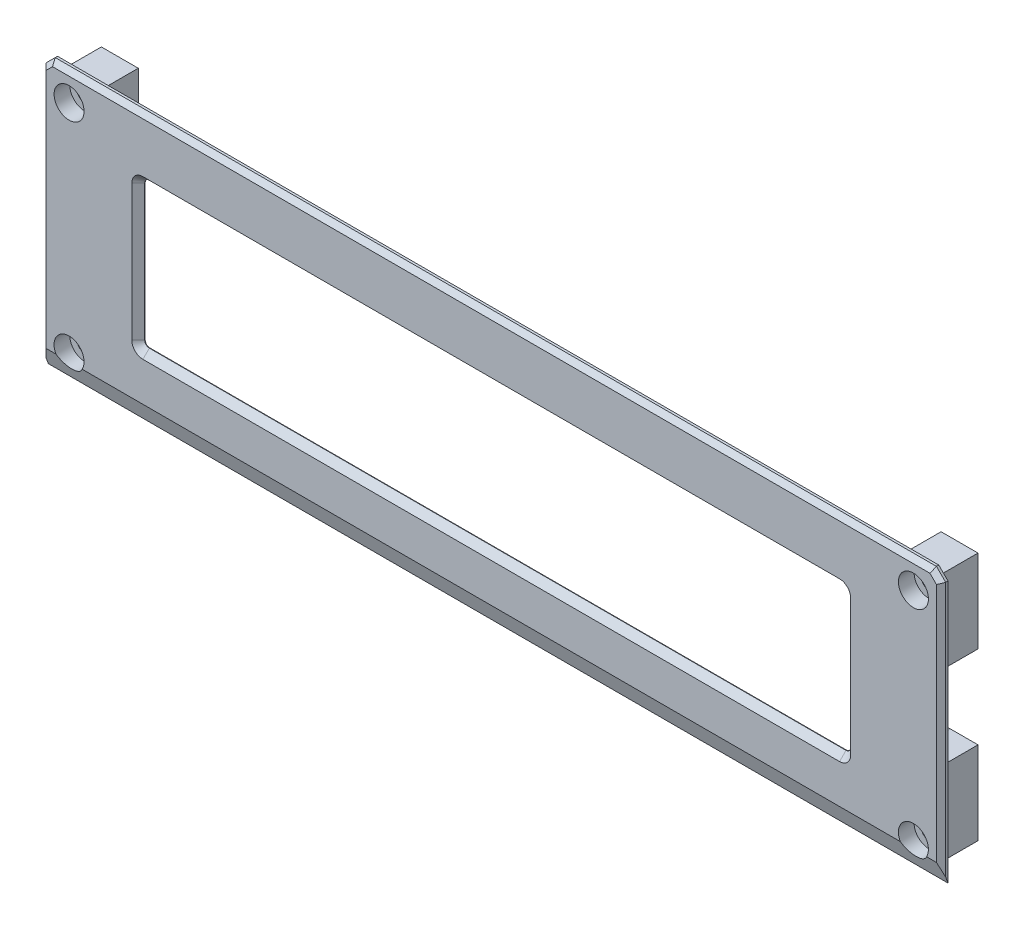
SolidWorks part; units mm, degrees
material "6061-T6 (SS)"
ref_plane "Front Plane" through (0, 0, 0) normal (0, 0, 1) x (1, 0, 0)
ref_plane "Top Plane" through (0, 0, 0) normal (0, 1, 0) x (1, 0, 0)
ref_plane "Right Plane" through (0, 0, 0) normal (1, 0, 0) x (0, 0, -1)
sketch "Croquis1" plane through (0, 0, 0) normal (0, 0, 1) x (1, 0, 0)
  line L0 (-78, 17.26) -> (78, 17.26) construction
  line L1 (-97.5, 29.5) -> (97.5, 29.5)
  line L2 (-97.5, 29.5) -> (-97.5, -29.2)
  line L3 (-97.5, -29.2) -> (97.5, -29.2)
  line L4 (97.5, 29.5) -> (97.5, -29.2)
  line L5 (-76.5, 16.26) -> (76.5, 16.26)
  line L6 (-76.5, 16.26) -> (-76.5, -15.24)
  line L7 (-76.5, -15.24) -> (76.5, -15.24)
  line L8 (76.5, 16.26) -> (76.5, -15.24)
  line L9 (78, -15.74) -> (-78, -15.74) construction
  line L10 (-81.5, -12.24) -> (-81.5, 13.76) construction
  line L11 (81.5, 13.76) -> (81.5, -12.24) construction
  line L14 (-97.5, 27.5) -> (-97.5, -29.2) construction
  line L15 (95.5, 29.5) -> (-95.5, 29.5) construction
  dimension "D1" = 1
  dimension "D2" = 0.5
  dimension "D3" = 5
  dimension "D4" = 5
extrude "Saliente-Extruir1" add sketch "Croquis1" along normal blind 1.5
fillet "Redondeo1" radius 1 4 edges at (-76.5, -15.24, 0.75) (76.5, -15.24, 0.75) (76.5, 16.26, 0.75) (-76.5, 16.26, 0.75)
chamfer "Chaflán1" distance 1.4 angle 45 8 edges at (0, -15.24, 1.5) (76.5, 0.51, 1.5) (0, 16.26, 1.5) (-76.5, 0.51, 1.5) (76.2071, 15.9671, 1.5) (76.2071, -14.9471, 1.5) (-76.2071, 15.9671, 1.5) (-76.2071, -14.9471, 1.5)
sketch "Croquis2" plane through (97.5, 0, 0) normal (1, 0, 0) x (0, 0, -1)
  line L0 (0, -29.2) -> (-1.5, -25.0788)
  line L1 (2.3196, -35.573) -> (0, -29.2) construction
  line L2 (0, -29.2) -> (-1.5, -29.2)
  line L3 (-1.5, -29.2) -> (-1.5, -25.0788)
  line L4 (-1.5, -29.2) -> (-1.5, 29.5) construction
extrude "Cortar-Extruir1" cut sketch "Croquis2" against normal through all
sketch "Croquis3" plane through (0, 0, 0) normal (0, 0, -1) x (-1, 0, 0)
  line L1 (-95, 27) -> (-87, 27)
  line L2 (-95, 27) -> (-95, 9)
  line L3 (-95, 9) -> (-87, 9)
  line L4 (-87, 27) -> (-87, 9)
  line L5 (-95, -27) -> (-87, -27)
  line L6 (-95, -27) -> (-95, -9)
  line L7 (-95, -9) -> (-87, -9)
  line L8 (-87, -27) -> (-87, -9)
  line L9 (95, 27) -> (87, 27)
  line L10 (95, 27) -> (95, 17)
  line L11 (95, 17) -> (87, 17)
  line L12 (87, 27) -> (87, 17)
  line L13 (95, -27) -> (87, -27)
  line L14 (95, -27) -> (95, -17)
  line L15 (95, -17) -> (87, -17)
  line L16 (87, -27) -> (87, -17)
  dimension "D1" = 8
  dimension "D2" = 18
  dimension "D3" = 18
  dimension "D4" = 10
  dimension "D5" = 10
extrude "Saliente-Extruir2" add sketch "Croquis3" along normal blind 9
sketch "Croquis4" plane through (0, 0, 0) normal (0, 0, -1) x (-1, 0, 0)
  line L0 (-87, 9) -> (-87, 27) construction
  line L1 (87, 27) -> (-87, 27)
  line L2 (87, 27) -> (87, 23)
  line L3 (87, 23) -> (-87, 23)
  line L4 (-87, 27) -> (-87, 23)
  line L5 (87, -17) -> (87, -27) construction
  line L6 (-87, -27) -> (87, -27)
  line L7 (-87, -27) -> (-87, -23)
  line L8 (-87, -23) -> (87, -23)
  line L9 (87, -27) -> (87, -23)
  line L10 (-95, 9) -> (-87, 9) construction
  line L11 (-95, -9) -> (-91, -9)
  line L12 (-95, -9) -> (-95, 9)
  line L13 (-95, 9) -> (-91, 9)
  line L14 (-91, -9) -> (-91, 9)
  line L15 (87, 17) -> (95, 17) construction
  line L16 (95, -17) -> (91, -17)
  line L17 (95, -17) -> (95, 17)
  line L18 (95, 17) -> (91, 17)
  line L19 (91, -17) -> (91, 17)
  point P12 (87, -25)
  dimension "D1" = 4
  dimension "D2" = 4
  dimension "D3" = 4
  dimension "D4" = 4
extrude "Saliente-Extruir3" add sketch "Croquis4" along normal blind 2
fillet "Redondeo2" radius 2 12 edges at (-87, 17, -4.5) (-87, -17, -4.5) (87, -9, -4.5) (87, 9, -4.5) (91, -9, -1) (87, -23, -1) (-87, -23, -1) (-91, -17, -1) (-91, 17, -1) (-87, 23, -1) (87, 23, -1) (91, 9, -1)
hole_wizard "Refrentado para tornillo con cabeza hueca de M31" positions "Croquis5" profile "Croquis7" counterbore size "M3" standard "DIN" end condition through all
sketch "Croquis5" plane through (0, 0, 1.5) normal (0, 0, 1) x (1, 0, 0)
  point P0 (-91.5, 23.5)
  point P3 (-91.5, -23.5)
  point P6 (91.5, -23.5)
  point P9 (91.5, 23.5)
sketch "Croquis7" plane through (-91.5, 23.5, 1.5) normal (1, 0, 0) x (0, -1, 0)
  line L0 (0, 0) -> (0, 10.5)
  line L1 (0, 10.5) -> (1.7, 10.5)
  line L3 (1.7, 10.5) -> (1.7, 3.4)
  line L4 (1.7, 3.4) -> (3.25, 3.4)
  line L5 (3.25, 3.4) -> (3.25, 0)
  line L7 (3.25, 0) -> (0, 0)
  line L11 (0, -6.35) -> (0, 107.95) construction
  dimension "Diámetro de taladro hasta el siguiente" = 3.4
  dimension "Profundidad de taladro hasta el siguiente" = 10.5
  dimension "Diámetro de refrentado" = 6.5
  dimension "Profundidad de refrentado" = 3.4
chamfer "Chaflán2" distance 2 angle 45 2 edges at (97.5, 29.5, 0.75) (-97.5, 29.5, 0.75)
chamfer "Chaflán3" distance 1 angle 45 5 edges at (97.5, 1.2106, 1.5) (96.5, 28.5, 1.5) (-97.5, 1.2106, 1.5) (-96.5, 28.5, 1.5) (0, 29.5, 1.5)
